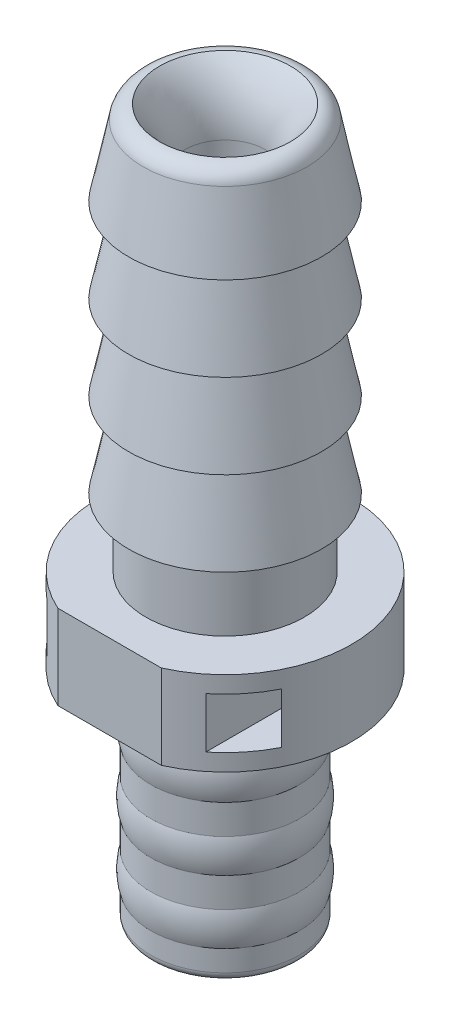
SolidWorks part; units mm, degrees
ref_plane "Front Plane" through (0, 0, 0) normal (0, 0, 1) x (1, 0, 0)
ref_plane "Top Plane" through (0, 0, 0) normal (0, 1, 0) x (1, 0, 0)
ref_plane "Right Plane" through (0, 0, 0) normal (1, 0, 0) x (0, 0, -1)
sketch "Sketch1" plane through (0, 0, 0) normal (0, 0, 1) x (1, 0, 0)
  line L0 (2.4, 42) -> (2.4, 0)
  line L1 (2.4, 0) -> (4.4, 0)
  line L2 (4.4, 0) -> (4.4, 1.75)
  line L3 (4.4, 9.25) -> (4.4, 7.5)
  line L4 (4.4, 5.5) -> (4.4, 3.75)
  line L6 (7.5, 13) -> (7.5, 18)
  line L7 (7.5, 18) -> (4.7, 18)
  line L8 (4.7, 18) -> (4.7, 22)
  line L9 (4.7, 22) -> (5.7173, 22)
  line L10 (5.7173, 22) -> (4.7, 27)
  line L11 (4.7, 27) -> (5.7173, 27)
  line L12 (5.7173, 27) -> (4.7, 32)
  line L13 (4.7, 32) -> (5.7173, 32)
  line L14 (5.7173, 32) -> (4.7, 37)
  line L16 (4.7, 37) -> (5.7173, 37)
  line L17 (5.7173, 37) -> (4.7, 42)
  line L18 (4.7, 42) -> (2.4, 42)
  line L19 (0, 7.8369) -> (0, 11.7995) construction
  line L20 (3.55, 32) -> (3.55, 37) construction
  line L21 (3.55, 37) -> (3.55, 42) construction
  line L22 (4.4, 11.25) -> (4.4, 13)
  line L23 (4.4, 13) -> (7.5, 13)
  line L24 (4.55, 2.75) -> (4.55, 6.5) construction
  arc A3 (4.4, 11.25) -> (4.4, 9.25) centre (1.1417, 10.25) cw
  arc A4 (4.4, 7.5) -> (4.4, 5.5) centre (1.1417, 6.5) cw
  arc A5 (4.4, 1.75) -> (4.4, 3.75) centre (1.1417, 2.75) ccw
  point P26 (6.1, 18)
  point P30 (5.018, 6.5)
  point P33 (4.4, 5.5)
  point P34 (-2.2242, 4.9612)
  dimension "D2" = 9.4
  dimension "D3" = 15
  dimension "D4" = 4
  dimension "D5" = 5
  dimension "D6" = 11.5
  dimension "D7" = 5
  dimension "D8" = 8.8
  dimension "D9" = 2
  dimension "D10" = 0.3
  dimension "D11" = 2
  dimension "D12" = 7.5
revolve "Revolve1" add sketch "Sketch1" angle 360 about L19
fillet "Fillet1" radius 1 1 edges at (0, 42, -4.7)
sketch "Sketch2" plane through (0, 0, 0) normal (0, 0, 1) x (1, 0, 0)
  line L0 (6.7, 17) -> (4.7, 17)
  line L1 (6.7, 17) -> (6.7, 14)
  line L2 (4.7, 17) -> (4.7, 14)
  line L3 (6.7, 14) -> (4.7, 14)
  line L4 (7.5, 13) -> (7.5, 18) construction
  line L5 (6.7, 15.5) -> (7.5, 15.5) construction
  line L6 (0, 0) -> (0, 18) construction
  line L7 (6.7, 17) -> (4.7, 17)
  line L8 (6.7, 14) -> (4.7, 14)
  line L9 (-6.7, 14) -> (-4.7, 14)
  line L10 (-6.7, 17) -> (-4.7, 17)
  line L11 (-6.7, 14) -> (-4.7, 14)
  line L12 (-4.7, 17) -> (-4.7, 14)
  line L13 (-6.7, 17) -> (-6.7, 14)
  line L14 (-6.7, 17) -> (-4.7, 17)
  dimension "D1" = 0.8
  dimension "D2" = 2
  dimension "D3" = 3
revolve "Cut-Revolve1" cut sketch "Sketch2" angle 180 about L6 region at (5.7, 15.5, 0)
extrude "Cut-Extrude1" cut sketch "Sketch2<3>" along normal up to next contours L10 L13 L9 L12 | L3 L1 L0 L2 region at (5.7, 15.5, 0) region at (-5.7, 15.5, 0)
sketch "Sketch2<3>" plane through (0, 0, 0) normal (0, 0, 1) x (1, 0, 0) same geometry as "Sketch2"
sketch "Sketch3" plane through (0, 13, 0) normal (0, -1, 0) x (1, 0, 0)
  line L0 (3.0661, 6.8447) -> (-3.0661, 6.8447)
  circle A0 centre (0, 0) radius 7.5 construction
  arc A1 (-3.0661, 6.8447) -> (3.0661, 6.8447) centre (0, 0) cw
  dimension "D1" = 1
extrude "Cut-Extrude2" cut sketch "Sketch3" against normal up to next
fillet "Fillet2" radius 0.5 1 edges at (0, 0, -4.4)
fillet "Fillet3" radius 5 2 edges at (0, 42, -2.4) (0, 0, -2.4)
